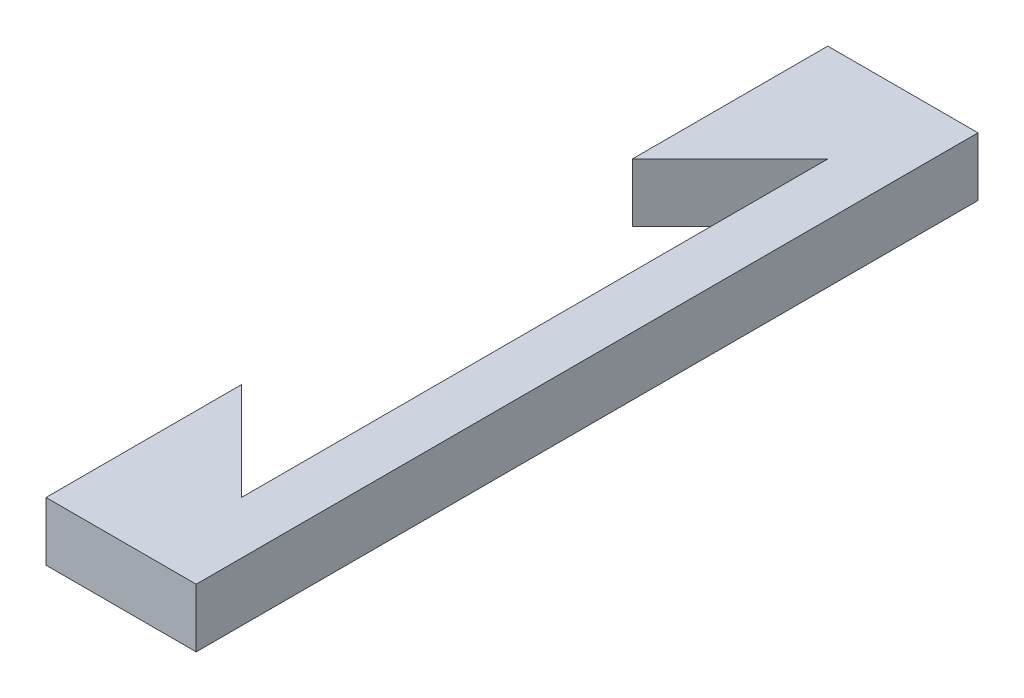
SolidWorks part; units mm, degrees
ref_plane "Alzado" through (0, 0, 0) normal (0, 0, 1) x (1, 0, 0)
ref_plane "Planta" through (0, 0, 0) normal (0, 1, 0) x (1, 0, 0)
ref_plane "Vista lateral" through (0, 0, 0) normal (1, 0, 0) x (0, 0, -1)
sketch "Croquis1" plane through (0, 0, 0) normal (0, 1, 0) x (1, 0, 0)
  line L0 (-67.5, 10) -> (-62.5, 15)
  line L1 (-67.5, -20) -> (67.5, -20)
  line L2 (-67.5, -20) -> (-67.5, -10)
  line L3 (-67.5, 20) -> (67.5, 20)
  line L4 (67.5, -20) -> (67.5, 20)
  line L5 (-67.5, -20) -> (67.5, 20) construction
  line L6 (-67.5, 20) -> (67.5, -20) construction
  line L7 (-62.5, 15) -> (-62.5, -15)
  line L8 (-62.5, -15) -> (-67.5, -10)
  line L9 (-67.5, 10) -> (-67.5, 20)
  line L11 (-42.5, 9.5) -> (-12.5, 9.5)
  line L12 (-42.5, 9.5) -> (-42.5, 12.5)
  line L13 (-42.5, 12.5) -> (-12.5, 12.5)
  line L14 (-12.5, 9.5) -> (-12.5, 12.5)
  line L15 (-42.5, 9.5) -> (-12.5, 12.5) construction
  line L16 (-42.5, 12.5) -> (-12.5, 9.5) construction
  line L17 (-42.5, -12.5) -> (-12.5, -12.5)
  line L18 (-42.5, -12.5) -> (-42.5, -9.5)
  line L19 (-42.5, -9.5) -> (-12.5, -9.5)
  line L20 (-12.5, -12.5) -> (-12.5, -9.5)
  line L21 (-42.5, -12.5) -> (-12.5, -9.5) construction
  line L22 (-42.5, -9.5) -> (-12.5, -12.5) construction
  circle A2 centre (46.714, 0) radius 11
  circle A3 centre (-52.5, 0) radius 2
  circle A4 centre (27.1858, 0) radius 1.9377
  circle A5 centre (12.1858, 0) radius 2
  point P0 (0, 0)
  point P8 (-62.5, 0)
  point P20 (-27.5, 11)
  point P28 (-27.5, -11)
  dimension "D6" = 15
  dimension "D7" = 22
  dimension "D11" = 10
  dimension "D12" = 4
  dimension "D1" = 40
  dimension "D2" = 135
  dimension "D3" = 45
  dimension "D4" = 20
  dimension "D5" = 30
  dimension "D8" = 30
  dimension "D9" = 3
  dimension "D10" = 40
  dimension "D13" = 12.5
  dimension "D14" = 12.5
extrude "Saliente-Extruir1" add sketch "Croquis1" along normal blind 3
sketch "Croquis2" plane through (0, 3, 0) normal (0, 1, 0) x (1, 0, 0)
  circle A0 centre (46.714, 0) radius 11
  circle A1 centre (46.714, 0) radius 13
  dimension "D1" = 2
extrude "Saliente-Extruir2" add sketch "Croquis2" along normal blind 4
sketch "Croquis3" plane through (0, 7, 0) normal (0, 1, 0) x (1, 0, 0)
  circle A0 centre (46.714, 0) radius 13
  circle A1 centre (46.714, 0) radius 9
  dimension "D1" = 18
extrude "Saliente-Extruir3" add sketch "Croquis3" along normal blind 2
chamfer "Chaflán1" distance 2 angle 45 1 edges at (46.714, 9, 13)
chamfer "Chaflán2" distance 10 angle 45 2 edges at (67.5, 1.5, -20) (67.5, 1.5, 20)
sketch "Croquis4" plane through (0, 3, 0) normal (0, 1, 0) x (1, 0, 0)
  line L1 (-59.8155, 36.7376) -> (78.9392, 36.7376)
  line L2 (-59.8155, 36.7376) -> (-59.8155, -40.4761)
  line L3 (-59.8155, -40.4761) -> (78.9392, -40.4761)
  line L4 (78.9392, 36.7376) -> (78.9392, -40.4761)
extrude "Cortar-Extruir1" cut sketch "Croquis4" against normal blind 10 and the other way blind 10
